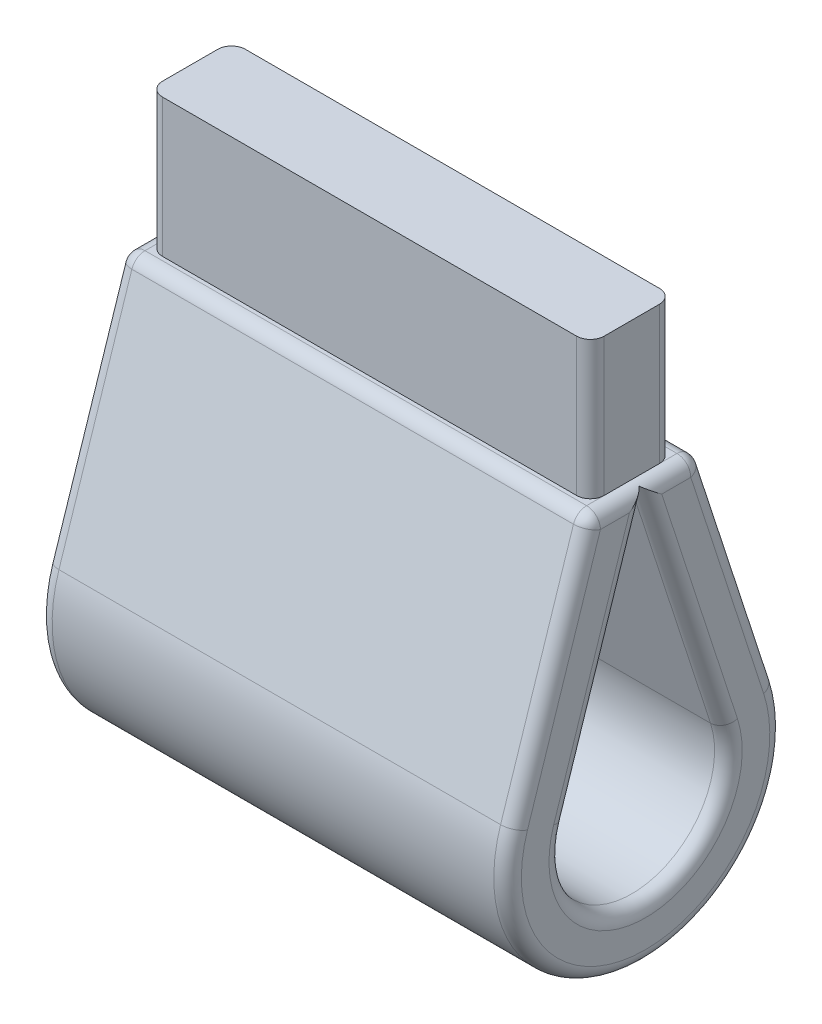
SolidWorks part; units mm, degrees
ref_plane "Front Plane" through (0, 0, 0) normal (0, 0, 1) x (1, 0, 0)
ref_plane "Top Plane" through (0, 0, 0) normal (0, 1, 0) x (1, 0, 0)
ref_plane "Right Plane" through (0, 0, 0) normal (1, 0, 0) x (0, 0, -1)
sketch "Sketch1" plane through (0, 0, 0) normal (1, 0, 0) x (0, 0, -1)
  line L0 (-5.7047, 1.8591) -> (0, 19.3647)
  line L1 (-9.5079, 3.0984) -> (-4, 20)
  line L2 (-4, 20) -> (-4, 30)
  line L3 (-4, 30) -> (4, 30)
  line L4 (4, 20) -> (4, 30)
  line L5 (-4, 20) -> (4, 20) construction
  line L6 (4, 20) -> (9.5079, 3.0984)
  line L7 (0, 19.3647) -> (5.7047, 1.8591)
  circle A0 centre (0, 0) radius 6 construction
  arc A1 (-9.5079, 3.0984) -> (9.5079, 3.0984) centre (0, 0) ccw
  arc A2 (-5.7047, 1.8591) -> (5.7047, 1.8591) centre (0, 0) ccw
  circle A3 centre (0, 0) radius 10 construction
  point P10 (10, 0)
  dimension "D1" = 12
  dimension "D3" = 8
  dimension "D4" = 30
  dimension "D5" = 10
  dimension "D2" = 4
extrude "Boss-Extrude1" add sketch "Sketch1" along normal blind 34
sketch "Sketch2" plane through (0, 30, 0) normal (0, 1, 0) x (1, 0, 0)
  line L4 (0, 4) -> (0, -4)
  line L5 (0, -4) -> (34, -4)
  line L6 (34, -4) -> (34, 4)
  line L7 (34, 4) -> (0, 4)
  line L8 (0, 4) -> (0, -4)
  line L9 (0, -4) -> (34, -4)
  line L10 (34, -4) -> (34, 4)
  line L11 (34, 4) -> (0, 4)
  line L16 (1, 3) -> (1, -3)
  line L17 (1, -3) -> (33, -3)
  line L18 (33, -3) -> (33, 3)
  line L19 (33, 3) -> (1, 3)
  line L20 (1, 3) -> (1, -3)
  line L21 (1, -3) -> (33, -3)
  line L22 (33, -3) -> (33, 3)
  line L23 (33, 3) -> (1, 3)
  dimension "D1" = 0
  dimension "D2" = 1
extrude "Cut-Extrude1" cut sketch "Sketch2" against normal up to vertex (10 mm away) up to point (0, 20, 4)
fillet "Fillet1" radius 1 16 edges at (34, 10.6119, -2.8524) (34, -6, 0) (34, 11.5492, -6.7539) (34, -10, 0) (0, 10.6119, 2.8524) (0, -6, 0) (0, 11.5492, -6.7539) (0, -10, 0) (34, 10.6119, 2.8524) (34, 20, 0) (34, 11.5492, 6.7539) (17, 20, -4) (17, 20, 4) (0, 10.6119, -2.8524) (0, 20, 0) (0, 11.5492, 6.7539)
fillet "Fillet2" radius 1 4 edges at (1, 25, -3) (1, 25, 3) (33, 25, -3) (33, 25, 3)
